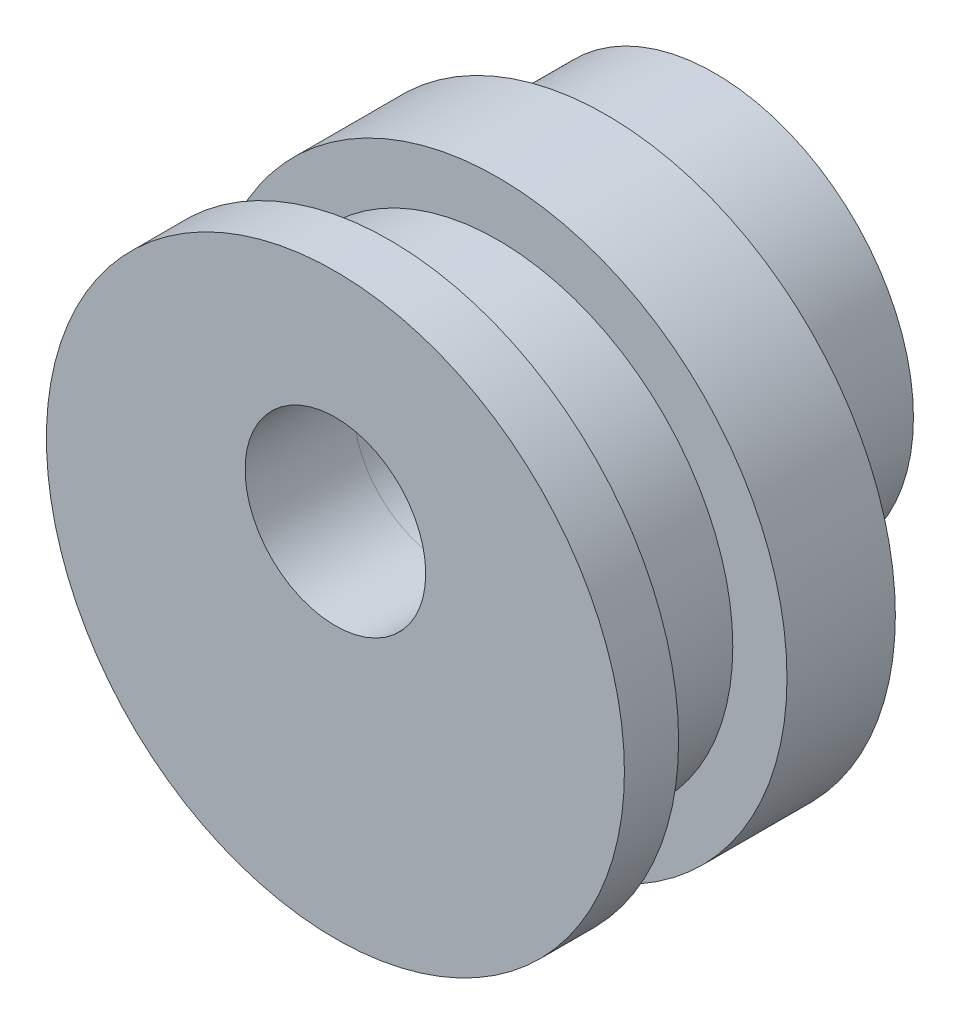
SolidWorks part; units mm, degrees
note: The reader was unsure of these and kept them because the rebuilt part matched: shared geometry of "Sketch1<4>", "Sketch1<5>", "Sketch2<3>".
material "Plain Carbon Steel"
ref_plane "Front Plane" through (0, 0, 0) normal (0, 0, 1) x (1, 0, 0)
ref_plane "Top Plane" through (0, 0, 0) normal (0, 1, 0) x (1, 0, 0)
ref_plane "Right Plane" through (0, 0, 0) normal (1, 0, 0) x (0, 0, -1)
sketch "Sketch1" plane through (0, 0, 0) normal (0, 0, 1) x (1, 0, 0)
  line L0 (0, 0) -> (8970.9912, 0) construction
  line L1 (0, 0) -> (0, -8970.9912) construction
  circle A0 centre (0, 0) radius 16
  circle A1 centre (0, 0) radius 13
  circle A2 centre (0, 4) radius 5
  circle A3 centre (0, 4) radius 11
  dimension "D1" = 32
  dimension "D2" = 26
  dimension "D3" = 10
  dimension "22" = 22
  dimension "D4" = 4
extrude "Boss-Extrude1" add sketch "Sketch1" along normal blind 6 contours A0 A3 A1 | A1 A3
extrude "Boss-Extrude2" add sketch "Sketch1<4>" along normal blind 12 contours A3 A1 | A1 A3 A2
sketch "Sketch1<4>" plane through (0, 0, 0) normal (0, 0, 1) x (1, 0, 0) same geometry as "Sketch1"
extrude "Boss-Extrude3" add sketch "Sketch1<5>" against normal blind 6 contours A1 A3 A2 | A1 A3
sketch "Sketch1<5>" plane through (0, 0, 0) normal (0, 0, 1) x (1, 0, 0) same geometry as "Sketch1"
sketch "Sketch2" plane through (0, 0, 12) normal (0, 0, 1) x (1, 0, 0)
  circle A0 centre (0, 0) radius 9.5
  circle A1 centre (0, 4) radius 5 construction
  circle A2 centre (0, 4) radius 5
  dimension "19" = 19
extrude "Cut-Extrude1" cut sketch "Sketch2" against normal blind 3
extrude "Boss-Extrude4" add sketch "Sketch2<3>" against normal blind 3 separate body
sketch "Sketch2<3>" plane through (0, 0, 12) normal (0, 0, 1) x (1, 0, 0) same geometry as "Sketch2"
sketch "Sketch3" plane through (0, 0, 12) normal (0, 0, 1) x (1, 0, 0)
  circle A0 centre (0, 0) radius 16
  circle A1 centre (0, 4) radius 5 construction
  circle A2 centre (0, 4) radius 5
  dimension "D1" = 32
extrude "Boss-Extrude5" add sketch "Sketch3" along normal blind 3
sketch "Sketch4" plane through (0, 0, 0) normal (0, 1, 0) x (1, 0, 0)
  line L0 (0, 0) -> (0, 50000) construction
  circle A0 centre (0, 3) radius 1.5
  dimension "D1" = 3
  dimension "3" = 3
extrude "Cut-Extrude2" cut sketch "Sketch4" against normal up to next contours A0
cosmetic thread "Cosmetic Thread9" parameters "D2"=4
pattern_circular "CirPattern1" count 2 every 45 about axis through (0, 4, -6) along (0, 0, 1) of "Cut-Extrude2"
cosmetic thread "Cosmetic Thread7" parameters "D2"=4
cosmetic thread "Cosmetic Thread10" parameters "D2"=4
mirror "Mirror1" about plane through (0, 0, 0) normal (1, 0, 0) of "CirPattern1"
cosmetic thread "Cosmetic Thread8" parameters "D2"=4
cosmetic thread "Cosmetic Thread11" parameters "D2"=4
cosmetic thread "Cosmetic Thread12" parameters "D2"=4
